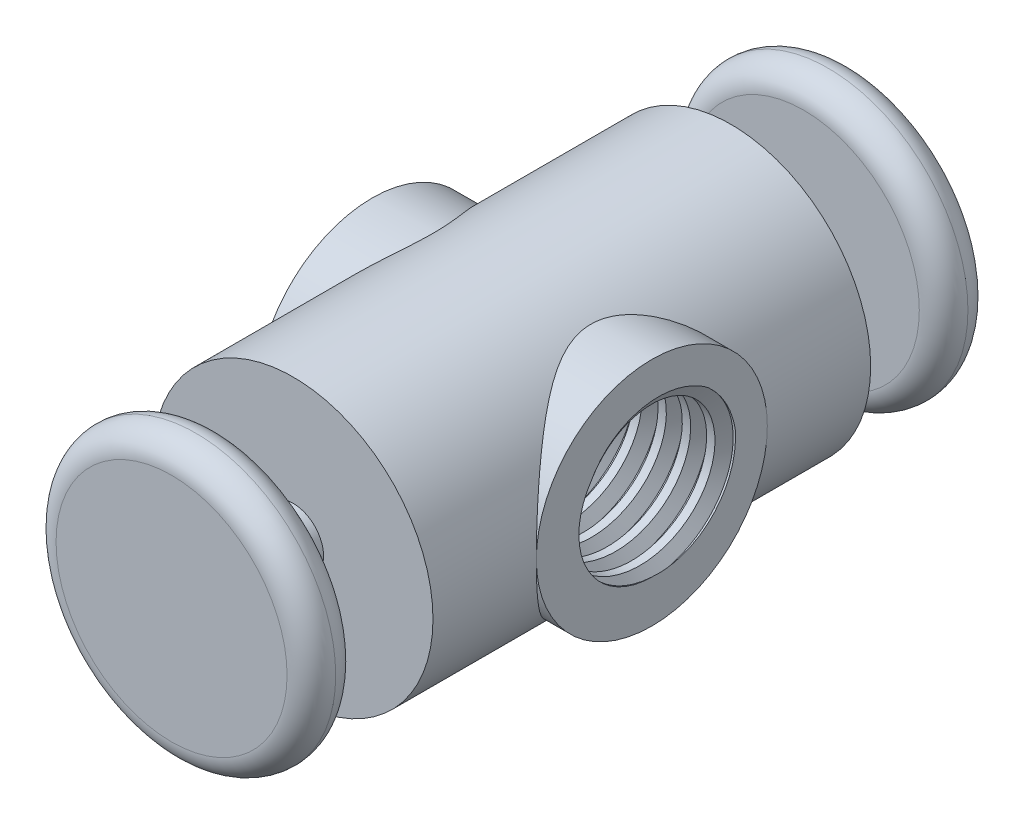
SolidWorks part; units mm, degrees
ref_plane "Front Plane" through (0, 0, 0) normal (0, 0, 1) x (1, 0, 0)
ref_plane "Top Plane" through (0, 0, 0) normal (0, 1, 0) x (1, 0, 0)
ref_plane "Right Plane" through (0, 0, 0) normal (1, 0, 0) x (0, 0, -1)
sketch "Sketch1" plane through (0, 0, 0) normal (0, 0, 1) x (1, 0, 0)
  circle A0 centre (0, 0) radius 11.5
  dimension "D1" = 23
extrude "Boss-Extrude1" add sketch "Sketch1" along normal blind 18
sketch "Sketch2" plane through (0, 0, 18) normal (0, 0, 1) x (1, 0, 0)
  circle A0 centre (0, 0) radius 2.5
  dimension "D1" = 5
extrude "Boss-Extrude2" add sketch "Sketch2" along normal blind 6
sketch "Sketch3" plane through (0, 0, 24) normal (0, 0, 1) x (1, 0, 0)
  circle A1 centre (0, 0) radius 11.5
  circle A3 centre (0, 0) radius 11.5
  dimension "D1" = 0
extrude "Boss-Extrude3" add sketch "Sketch3" along normal blind 4
fillet "Fillet1" radius 2 2 edges at (11.5, 0, 24) (11.5, 0, 28)
mirror "Mirror1" about plane through (0, 0, 0) normal (0, 0, 1) of bodies 103 104
sketch "Sketch5" plane through (0, 0, 0) normal (1, 0, 0) x (0, 0, -1)
  circle A0 centre (0, 0) radius 6
  dimension "D1" = 12
extrude "Cut-Extrude2" cut sketch "Sketch5" against normal through all both and the other way through all
ref_plane "Plane1" through (11.5, 0, 0) normal (1, 0, 0) x (0, 0, -1)
sketch "Sketch6" plane through (11.5, 0, 0) normal (1, 0, 0) x (0, 0, -1)
  circle A1 centre (0, 0) radius 6 construction
  circle A2 centre (0, 0) radius 6
  circle A3 centre (0, 0) radius 9.5
  point P3 (0, 0)
  dimension "D1" = 3.5
extrude "Boss-Extrude4" add sketch "Sketch6" against normal blind 23
thread "Thread1" pitch 1.75 start angle 0, offset 1.5, length 0, pitch 2, diameter 12
ref_plane "Plane2" through (13, 0, 6) normal (0, -1, 0) x (0, 0, 1)
sketch "Thread Profile1" plane through (13, 0, 6) normal (0, -1, 0) x (0, 0, 1)
  line L0 (0, 0) -> (0, 1.75) construction
  line L1 (0, 0) -> (0.9472, 0.5469)
  line L2 (0.9472, 0.5469) -> (0.9472, 0.7656)
  line L3 (0.9472, 0.7656) -> (0, 1.3125)
  line L4 (0.9472, 0.6562) -> (0, 0.6562) construction
  line L11 (0, 0) -> (0, 1.3125)
  point P2 (0, 0)
  dimension "Pitch" = 1.75
  dimension "Profile_Angle" = 60
  dimension "Profile_Land" = 0.2188
  dimension "Profile_Height" = 0.9472
